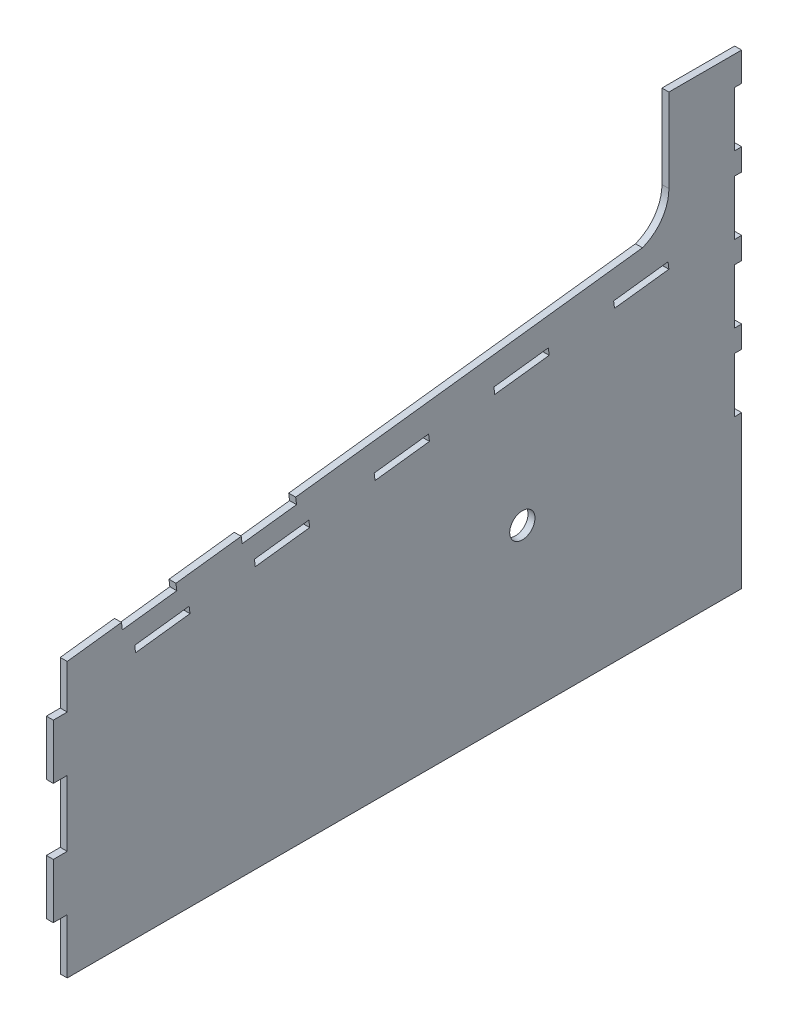
SolidWorks part; units mm, degrees
material "Beech"
ref_plane "Front Plane" through (0, 0, 0) normal (0, 0, 1) x (1, 0, 0)
ref_plane "Top Plane" through (0, 0, 0) normal (0, 1, 0) x (1, 0, 0)
ref_plane "Right Plane" through (0, 0, 0) normal (1, 0, 0) x (0, 0, -1)
sketch "Sketch1" plane through (0, 0, 0) normal (1, 0, 0) x (0, 0, -1)
  line L1 (0, 0) -> (615, 0)
  line L2 (0, 0) -> (0, 50)
  line L4 (615, 0) -> (615, 138.97)
  line L6 (615, 258.97) -> (615, 278.97)
  line L7 (615, 425.32) -> (548.65, 425.32)
  line L8 (548.65, 349.09) -> (548.65, 425.32)
  line L9 (0, 250) -> (615, 250) construction
  line L10 (524.53, 314.4042) -> (615, 325.5125) construction
  line L11 (-12.7, 160) -> (-12.7, 210)
  line L12 (0, 50) -> (-12.7, 50)
  line L14 (0, 100) -> (-12.7, 100)
  line L15 (-12.7, 50) -> (-12.7, 100)
  line L16 (0, 160) -> (-12.7, 160)
  line L18 (0, 210) -> (-12.7, 210)
  line L19 (0, 210) -> (0, 250)
  line L21 (0, 100) -> (0, 160)
  line L33 (0, 250) -> (524.53, 314.4042) construction
  line L34 (0, 250) -> (524.53, 314.4042)
  line L36 (615, 398.97) -> (608.65, 398.97)
  line L38 (615, 348.97) -> (608.65, 348.97)
  line L39 (608.65, 398.97) -> (608.65, 348.97)
  line L40 (615, 328.97) -> (608.65, 328.97)
  line L41 (608.65, 328.97) -> (608.65, 278.97)
  line L42 (615, 278.97) -> (608.65, 278.97)
  line L44 (615, 258.97) -> (608.65, 258.97)
  line L45 (608.65, 258.97) -> (608.65, 208.97)
  line L46 (615, 208.97) -> (608.65, 208.97)
  line L48 (615, 188.97) -> (608.65, 188.97)
  line L49 (608.65, 188.97) -> (608.65, 138.97)
  line L50 (615, 138.97) -> (608.65, 138.97)
  line L51 (615, 188.97) -> (615, 208.97)
  line L54 (615, 328.97) -> (615, 348.97)
  line L56 (615, 398.97) -> (615, 425.32)
  arc A0 (524.53, 314.4042) -> (548.65, 349.09) centre (511.65, 349.09) ccw
  dimension "D4" = 37
  dimension "D1" = 615
  dimension "D2" = 250
  dimension "D3" = 66.35
  dimension "D5" = 7
  dimension "D6" = 175.32
  dimension "D7" = 76.23
  dimension "D8" = 12.7
  dimension "D9" = 50
  dimension "D10" = 50
  dimension "D11" = 2
  dimension "D12" = 40
  dimension "D13" = 6.35
  dimension "D14" = 50
  dimension "D15" = 26.35
  dimension "D17" = 138.97
  dimension "D16" = 4
extrude "Boss-Extrude1" add sketch "Sketch1" along normal blind 6.35
sketch "Sketch2" plane through (6.35, 0, 0) normal (1, 0, 0) x (0, 0, -1)
  line L0 (514.5695, 313.1812) -> (615, 324.7758) construction
  line L1 (615, 0) -> (615, 138.97) construction
  line L2 (208.3168, 275.5781) -> (158.6895, 269.4846)
  line L3 (0, 224.4093) -> (615, 299.9218) construction
  line L4 (0, 50) -> (0, 0) construction
  line L5 (61.5379, 231.9651) -> (62.3117, 225.6625)
  line L6 (62.3117, 225.6625) -> (111.939, 231.7559)
  line L7 (111.939, 231.7559) -> (111.1652, 238.0586)
  line L8 (111.1652, 238.0586) -> (61.5379, 231.9651)
  line L9 (220.3452, 251.4642) -> (170.7179, 245.3708)
  line L10 (170.7179, 245.3708) -> (171.4918, 239.0681)
  line L11 (171.4918, 239.0681) -> (221.1191, 245.1616)
  line L12 (221.1191, 245.1616) -> (220.3452, 251.4642)
  line L13 (329.5253, 264.8699) -> (279.898, 258.7764)
  line L14 (279.898, 258.7764) -> (280.6719, 252.4737)
  line L15 (280.6719, 252.4737) -> (330.2992, 258.5672)
  line L16 (330.2992, 258.5672) -> (329.5253, 264.8699)
  line L17 (438.7054, 278.2755) -> (389.0781, 272.182)
  line L18 (389.0781, 272.182) -> (389.852, 265.8794)
  line L19 (389.852, 265.8794) -> (439.4793, 271.9728)
  line L20 (439.4793, 271.9728) -> (438.7054, 278.2755)
  line L21 (547.8855, 291.6811) -> (498.2582, 285.5877)
  line L22 (498.2582, 285.5877) -> (499.032, 279.285)
  line L23 (499.032, 279.285) -> (548.6593, 285.3785)
  line L24 (548.6593, 285.3785) -> (547.8855, 291.6811)
  line L25 (158.6895, 269.4846) -> (159.4634, 263.182)
  line L26 (524.53, 314.4042) -> (0, 250) construction
  line L27 (0, 224.4093) -> (-3.0955, 249.6199) construction
  line L28 (-3.0955, 249.6199) -> (0, 250) construction
  line L29 (49.5095, 256.079) -> (50.2833, 249.7763)
  line L30 (50.2833, 249.7763) -> (99.9106, 255.8698)
  line L31 (99.9106, 255.8698) -> (99.1368, 262.1725)
  line L32 (99.1368, 262.1725) -> (49.5095, 256.079)
  line L33 (159.4634, 263.182) -> (209.0907, 269.2754)
  line L34 (209.0907, 269.2754) -> (208.3168, 275.5781)
  line L35 (0, 0) -> (615, 0) construction
  line L36 (615, 0) -> (615, 138.97) construction
  circle A0 centre (415, 150) radius 11.5
  point P45 (0, 0)
  point P48 (0, 0)
  dimension "D12" = 23
  dimension "D1" = 25.4
  dimension "D2" = 50
  dimension "D3" = 6.35
  dimension "D4" = 62
  dimension "D5" = 90
  dimension "D6" = 6.35
  dimension "D7" = 53
  dimension "D8" = 50
  dimension "D10" = 150
  dimension "D11" = 200
  dimension "D9" = 2
extrude "Cut-Extrude1" cut sketch "Sketch2" against normal blind 6.35
